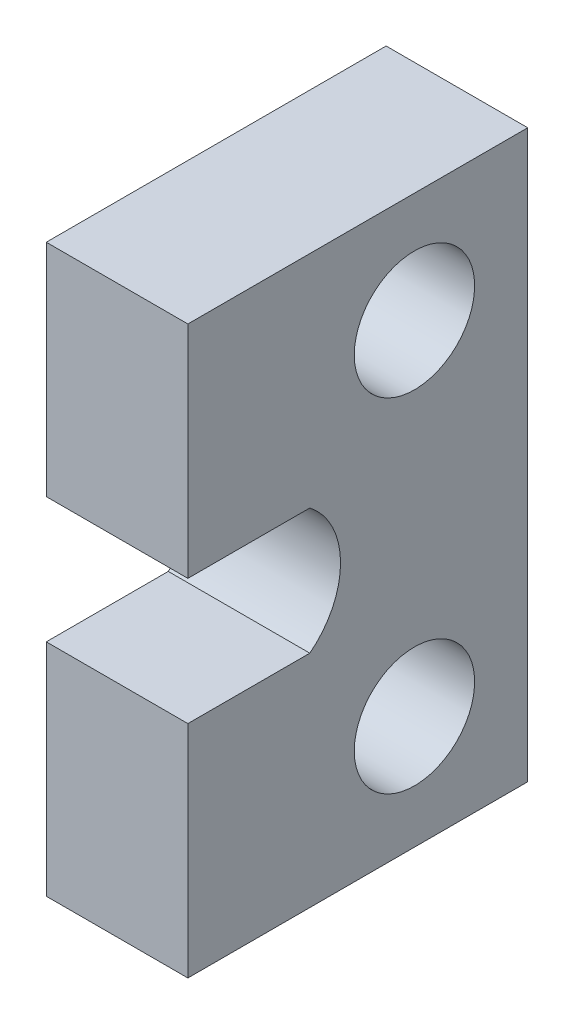
SolidWorks part; units mm, degrees
ref_plane "Front Plane" through (0, 0, 0) normal (0, 0, 1) x (1, 0, 0)
ref_plane "Top Plane" through (0, 0, 0) normal (0, 1, 0) x (1, 0, 0)
ref_plane "Right Plane" through (0, 0, 0) normal (1, 0, 0) x (0, 0, -1)
sketch "Sketch1" plane through (0, 0, 0) normal (0, 0, 1) x (1, 0, 0)
  line L1 (0, 0) -> (15.875, 0)
  line L2 (0, 0) -> (0, 63.5)
  line L3 (0, 63.5) -> (15.875, 63.5)
  line L4 (15.875, 0) -> (15.875, 63.5)
  dimension "D1" = 63.5
  dimension "D2" = 15.875
extrude "Boss-Extrude1" add sketch "Sketch1" along normal blind 38.1
sketch "Sketch2" plane through (0, 0, 0) normal (-1, 0, 0) x (0, 0, 1)
  line L0 (0, 31.75) -> (31.75, 31.75)
  line L1 (37.2412, 38.7985) -> (24.428, 38.7985)
  line L2 (24.428, 24.7015) -> (37.2412, 24.7015)
  line L3 (30.8346, 38.7985) -> (30.8346, 24.7015)
  line L4 (24.428, 38.7985) -> (0, 38.7985)
  line L5 (24.428, 24.7015) -> (0, 24.7015)
  line L6 (0, 63.5) -> (0, 0) construction
  line L7 (38.1, 63.5) -> (38.1, 0) construction
  line L8 (37.2412, 38.7985) -> (38.1, 38.7985)
  line L9 (37.2412, 38.7985) -> (37.2412, 24.7015)
  line L10 (37.2412, 24.7015) -> (38.1, 24.7015)
  line L11 (38.1, 38.7985) -> (38.1, 24.7015)
  arc A0 (37.2412, 38.7985) -> (37.2412, 24.7015) centre (31.75, 31.75) cw
  arc A1 (24.428, 38.7985) -> (24.428, 24.7015) centre (29.9192, 31.75) ccw
  point P10 (40.685, 31.75)
  point P17 (0, 31.75)
  dimension "D1" = 31.75
  dimension "D2" = 12.8132
  dimension "D3" = 12.8132
  dimension "D4" = 14.097
  dimension "D5" = 8.935
extrude "Cut-Extrude1" cut sketch "Sketch2" against normal through all contours L1 A1 L0 L3 | L0 A1 L2 L3 | L9 L1 L3 L2 | A0 L11 L9 | A0 L11 | L9 L8 L11 L10 | A1 L2 A0 L1 region at (0, 35.057, 26.3751) region at (0, 28.443, 26.3751) region at (0, 31.75, 34.0379) region at (0, 31.75, 37.6624) region at (0, 31.75, 39.148)
sketch "Sketch3" plane through (0, 0, 0) normal (-1, 0, 0) x (0, 0, 1)
  line L0 (12.7, 0) -> (12.7, 12.7)
  line L2 (12.7, 63.8492) -> (12.7, 51.1493)
  line L4 (0, 51.1493) -> (12.7, 51.1493)
  line L5 (0, 63.5) -> (0, 0) construction
  circle A0 centre (12.7, 51.1493) radius 6.7469
  circle A1 centre (12.7, 12.7) radius 6.7469
  point P11 (0, 0)
  dimension "D3" = 13.4937
  dimension "D4" = 13.4937
  dimension "D1" = 12.7
  dimension "D2" = 12.7
  dimension "D5" = 12.7
extrude "Cut-Extrude2" cut sketch "Sketch3" against normal through all contours A0 | A1 | A0 region at (0, 50.1948, 13.6545) region at (0, 8.0642, 17.3358)
equation "\"D2@Sketch3\"=\"D1@Sketch3\""
equation "\"D4@Sketch3\"=\"D3@Sketch3\""
equation "\"D5@Sketch3\"=\"D1@Sketch3\""
